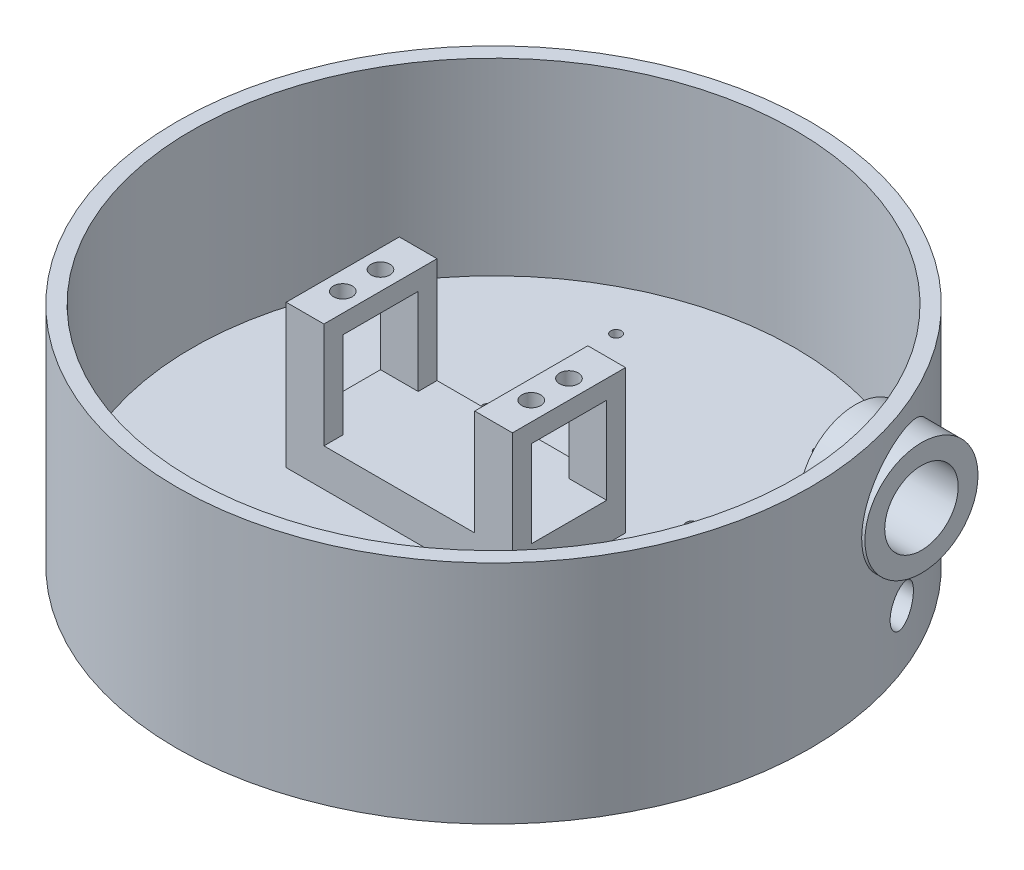
SolidWorks part; units mm, degrees
ref_plane "Front Plane" through (0, 0, 0) normal (0, 0, 1) x (1, 0, 0)
ref_plane "Top Plane" through (0, 0, 0) normal (0, 1, 0) x (1, 0, 0)
ref_plane "Right Plane" through (0, 0, 0) normal (1, 0, 0) x (0, 0, -1)
sketch "Sketch1" plane through (0, 0, 0) normal (0, 1, 0) x (1, 0, 0)
  circle A0 centre (0, 0) radius 84
extrude "base" add sketch "Sketch1" along normal blind 10
sketch "Sketch2" plane through (0, 10, 0) normal (0, 1, 0) x (1, 0, 0)
  circle A0 centre (0, 0) radius 84
  circle A1 centre (0, 0) radius 80
extrude "walls" add sketch "Sketch2" along normal blind 50
sketch "Sketch3" plane through (0, 10, 0) normal (0, 1, 0) x (1, 0, 0)
  line L0 (0, 0) -> (10, 0)
  line L1 (10, -15) -> (10, 15)
  line L2 (10, 15) -> (20.0065, 15)
  line L3 (20.0065, 15) -> (20.0065, -15)
  line L4 (20.0065, -15) -> (10, -15)
  line L6 (10, 10) -> (20.0065, 10)
  line L7 (20.0065, -10) -> (10, -10)
  line L8 (-30, -15) -> (-30, 15)
  line L9 (-30, 15) -> (-40, 15)
  line L10 (-40, 15) -> (-40, -15)
  line L11 (-40, -15) -> (-30, -15)
  line L12 (-30, 10) -> (-40, 10)
  line L13 (-40, -10) -> (-30, -10)
  line L14 (0, 0) -> (-40, 0)
  point P7 (10, 0)
  point P16 (-30, 0)
  dimension "D1" = 10.0065
  dimension "D2" = 30
  dimension "D3" = 10
  dimension "D4" = 5
  dimension "D5" = 5
  dimension "D6" = 5
  dimension "D7" = 5
  dimension "D8" = 40
  dimension "D9" = 10
  dimension "D10" = 10
  dimension "D11" = 10
  dimension "D12" = 30
extrude "motor mount 1" add sketch "Sketch3" along normal blind 38 contours L1 L6 L3 L2 | L3 L7 L1 L4 region at (15.0032, 10, 12.5) region at (15.0032, 10, -12.5)
extrude "motor mount 2" add sketch "Sketch3<5>" along normal blind 38 contours L12 L8 L9 L10 | L13 L10 L11 L8 region at (-35, 10, 12.5) region at (-35, 10, -12.5)
sketch "Sketch3<5>" plane through (0, 10, 0) normal (0, 1, 0) x (1, 0, 0) same geometry as "Sketch3"
sketch "Sketch6" plane through (0, 48, 0) normal (0, 1, 0) x (1, 0, 0)
  line L4 (10, 10) -> (20.0065, 10)
  line L5 (20.0065, 10) -> (20.0065, -10)
  line L6 (20.0065, -10) -> (10, -10)
  line L7 (10, -10) -> (10, 10)
  line L8 (-30, 10) -> (-30, -10)
  line L9 (-30, -10) -> (-40, -10)
  line L10 (-40, -10) -> (-40, 10)
  line L11 (-40, 10) -> (-30, 10)
  circle A0 centre (-35, 5) radius 2.5
  circle A1 centre (-35, -5) radius 2.5
  circle A2 centre (15, 5) radius 2.5
  circle A3 centre (15, -5) radius 2.5
  dimension "D9" = 5
  dimension "D10" = 5
  dimension "D11" = 5
  dimension "D12" = 5
  dimension "D1" = 5
  dimension "D2" = 10
  dimension "D3" = 5
  dimension "D4" = 5
  dimension "D5" = 5
  dimension "D6" = 5
  dimension "D7" = 10
  dimension "D8" = 5
extrude "motor screw holes" add sketch "Sketch6" against normal blind 5
sketch "Sketch7" plane through (0, 10, 0) normal (0, 1, 0) x (1, 0, 0)
  line L0 (-30, 25.5) -> (-27, 25.5)
  line L1 (-30, 62.5) -> (30, 62.5)
  line L2 (-30, 62.5) -> (-30, 22.5)
  line L3 (-30, 22.5) -> (30, 22.5)
  line L4 (30, 62.5) -> (30, 22.5)
  line L5 (-27, 25.5) -> (-27, 22.5)
  line L6 (-27, 62.5) -> (-27, 59.5)
  line L7 (-27, 59.5) -> (-30, 59.5)
  line L8 (30, 59.5) -> (27, 59.5)
  line L9 (27, 59.5) -> (27, 62.5)
  line L10 (30, 25.5) -> (27, 25.5)
  line L11 (27, 25.5) -> (27, 22.5)
  circle A0 centre (-27, 59.5) radius 1.4
  circle A1 centre (-27, 25.5) radius 1.4
  circle A2 centre (27, 25.5) radius 1.4
  circle A3 centre (27, 59.5) radius 1.4
  dimension "D1" = 60
  dimension "4" = 40
  dimension "D2" = 30
  dimension "D3" = 22.5
  dimension "D4" = 3
  dimension "D5" = 3
  dimension "D6" = 3
  dimension "D7" = 3
  dimension "D8" = 3
  dimension "D9" = 3
  dimension "D10" = 3
  dimension "D11" = 3
extrude "perfboard screw holes" cut sketch "Sketch7" against normal blind 6 contours A3 | A0 | A1 | A2
sketch "Sketch9" plane through (0, 10, 0) normal (0, 1, 0) x (1, 0, 0)
  line L0 (-30, 15) -> (10, 15)
  line L1 (10, 15) -> (10, -15)
  line L2 (10, -15) -> (-30, -15)
  line L3 (-30, -15) -> (-30, 15)
  line L4 (-40, 10) -> (-30, 10)
  line L5 (-30, 10) -> (-40, 10) construction
  line L6 (-40, 10) -> (-40, -10)
  line L7 (-40, -10) -> (-30, -10)
  line L8 (-40, -10) -> (-30, -10) construction
  line L9 (10, 10) -> (20.0065, 10)
  line L10 (10, 10) -> (20.0065, 10) construction
  line L11 (20.0065, 10) -> (20.0065, -10)
  line L12 (20.0065, -10) -> (10, -10)
  line M5 (-40, -10) -> (-30, -10)
  line M6 (-30, -10) -> (-30, -15)
  line M9 (-30, 10) -> (-40, 10)
  line M12 (-30, 15) -> (-30, 10)
  line M15 (10, -15) -> (10, -10)
  line M16 (10, -10) -> (20.0065, -10)
  line M17 (10, 10) -> (10, 15)
  line M20 (20.0065, 10) -> (10, 10)
extrude "Boss-Extrude1" add sketch "Sketch9" along normal blind 10 contours L6 L3 M9 M5 | L3 L2 L1 L0 M6 M15 M17 M12 | L11 L1 M20 M16 region at (-10, 10, 0) region at (-35, 10, 0) region at (15.0032, 10, 0)
sketch "Sketch10" plane through (0, 0, 0) normal (1, 0, 0) x (0, 0, -1)
  circle A0 centre (30, 40) radius 9.75
  circle A1 centre (30, 40) radius 15
  circle A2 centre (30, 15) radius 5
  dimension "D2" = 30
  dimension "D3" = 19.5
  dimension "D6" = 10
  dimension "D1" = 30
  dimension "D4" = 40
  dimension "D5" = 25
  dimension "D7" = 30
extrude "Cut-Extrude1" cut sketch "Sketch10" along normal through all contours A0 | A2 region at (0, 40, -30)
extrude "Boss-Extrude2" add sketch "Sketch10<3>" along normal blind 17.5 from offset 66 contours A1 A0 region at (0, 40, -15.4243)
sketch "Sketch10<3>" plane through (0, 0, 0) normal (1, 0, 0) x (0, 0, -1) same geometry as "Sketch10"
equation "\"6..50cm\"=7"
